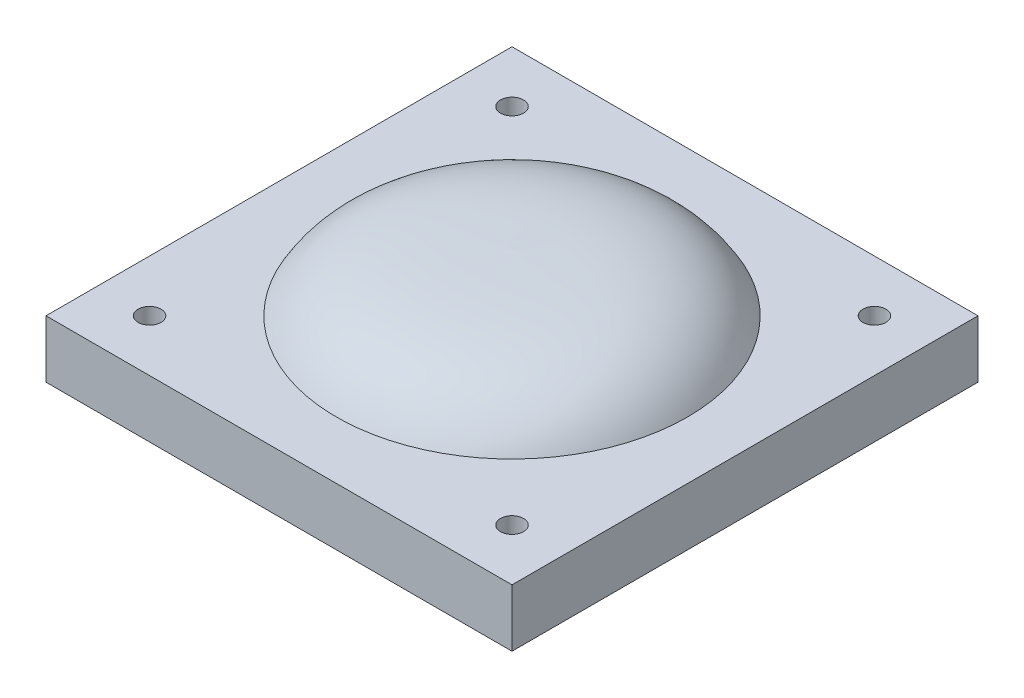
SolidWorks part; units mm, degrees
ref_plane "Front" through (0, 0, 0) normal (0, 0, 1) x (1, 0, 0)
ref_plane "Top" through (0, 0, 0) normal (0, 1, 0) x (1, 0, 0)
ref_plane "Right" through (0, 0, 0) normal (1, 0, 0) x (0, 0, -1)
sketch "Sketch1" plane through (0, 0, 0) normal (0, 0, 1) x (1, 0, 0)
  line L0 (0, 25) -> (0, 10) construction
  line L1 (31.5, 19.8898) -> (31.5, -17.8473) construction
  line L2 (0, 0) -> (31.5, 0) construction
  line L3 (0, 25) -> (0, 0) construction
  line L4 (31.5, 0) -> (30.5, 0) construction
  line L5 (0, 10) -> (0, 0)
  line L6 (0, 0) -> (30.5, 0)
  spline S0 degree 3 poles (0, 25) (1.3715, 25) (4.0902, 24.3027) (10.7515, 17.1368) (25.5788, 15.0702) (31.0385, 6.4502) (31.5, 0) knots 0 0 0 0 0.091246 0.195023 0.675457 1 1 1 1 construction
  spline S1 degree 3 poles (30.5, 0) (24.4624, 10.5881) (11.1572, 9.4928) (0, 10) knots 0 0 0 0 1 1 1 1
  dimension "D1" = 25
  dimension "D4" = 31.5
  dimension "D2" = 1
  dimension "D3" = 15
revolve "Revolve1" add sketch "Sketch1" angle 360 about L5
sketch "Sketch2" plane through (0, 0, 0) normal (0, 1, 0) x (1, 0, 0)
  line L1 (-40.5, -40.5) -> (40.5, -40.5)
  line L2 (-40.5, -40.5) -> (-40.5, 40.5)
  line L3 (-40.5, 40.5) -> (40.5, 40.5)
  line L4 (40.5, -40.5) -> (40.5, 40.5)
  line L5 (-40.5, -40.5) -> (40.5, 40.5) construction
  line L6 (-40.5, 40.5) -> (40.5, -40.5) construction
  point P0 (0, 0)
  dimension "D1" = 81
extrude "Boss-Extrude1" add sketch "Sketch2" against normal blind 10
sketch "Sketch3" plane through (0, 0, 0) normal (0, 1, 0) x (1, 0, 0)
  line L0 (40.5, 40.5) -> (-40.5, 40.5) construction
  line L1 (-40.5, 40.5) -> (-40.5, -40.5) construction
  line L2 (0, 0) -> (0, 40.5) construction
  line L3 (0, 0) -> (-40.5, 0) construction
  circle A0 centre (-31.5, 31.5) radius 2
  circle A1 centre (-31.5, -31.5) radius 2
  circle A2 centre (31.5, -31.5) radius 2
  circle A3 centre (31.5, 31.5) radius 2
  dimension "D3" = 4
  dimension "D1" = 9
  dimension "D2" = 9
extrude "Cut-Extrude1" cut sketch "Sketch3" against normal through all
equation "\"CutAngle\"= 2"
